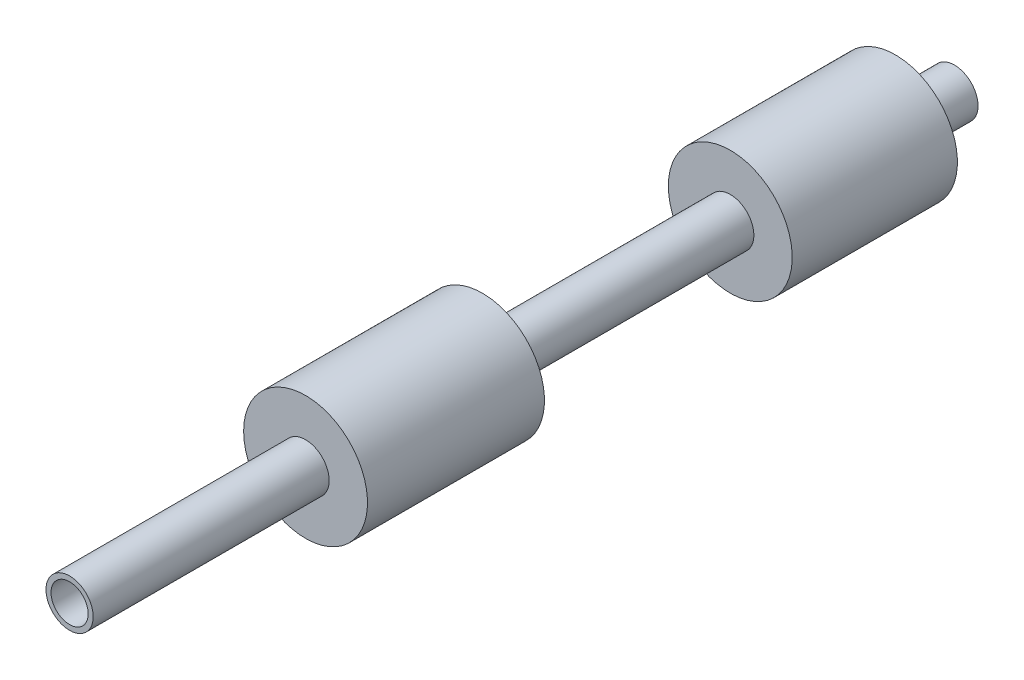
SolidWorks part; units mm, degrees
ref_plane "前视基准面" through (0, 0, 0) normal (0, 0, 1) x (1, 0, 0)
ref_plane "上视基准面" through (0, 0, 0) normal (0, 1, 0) x (1, 0, 0)
ref_plane "右视基准面" through (0, 0, 0) normal (1, 0, 0) x (0, 0, -1)
sketch "草图1" plane through (0, 0, 0) normal (0, 0, 1) x (1, 0, 0)
  circle A0 centre (0, 0) radius 3.15
  circle A1 centre (0, 0) radius 4
  dimension "D1" = 6.3
  dimension "D3" = 8
  dimension "D2" = 0.85
extrude "凸台-拉伸1" add sketch "草图1" along normal blind 149
sketch "草图3" plane through (0, 0, 0) normal (0, 0, -1) x (-1, 0, 0)
  circle A2 centre (0, 0) radius 4
  circle A3 centre (0, 0) radius 4
  dimension "D1" = 0
extrude "凸台-拉伸2" add sketch "草图3" along normal blind 1
sketch "草图4" plane through (0, 0, -1) normal (0, 0, -1) x (-1, 0, 0)
  circle A0 centre (0, 0) radius 4 construction
  circle A1 centre (0, 0) radius 4
  circle A3 centre (0, 0) radius 10.5
  dimension "D1" = 21
extrude "凸台-拉伸4" add sketch "草图4<2>" against normal blind 30 from offset 80 offset against normal yes
sketch "草图4<2>" plane through (0, 0, -1) normal (0, 0, -1) x (-1, 0, 0) same geometry as "草图4"
extrude "凸台-拉伸3" add sketch "草图4" against normal blind 28 from offset 10 offset against normal yes
sketch "草图5" plane through (0, 0, -1) normal (0, 0, -1) x (-1, 0, 0)
  circle A0 centre (0, 0) radius 3.15
  dimension "D1" = 6.3
extrude "切除-拉伸1" cut sketch "草图5" against normal blind 10
